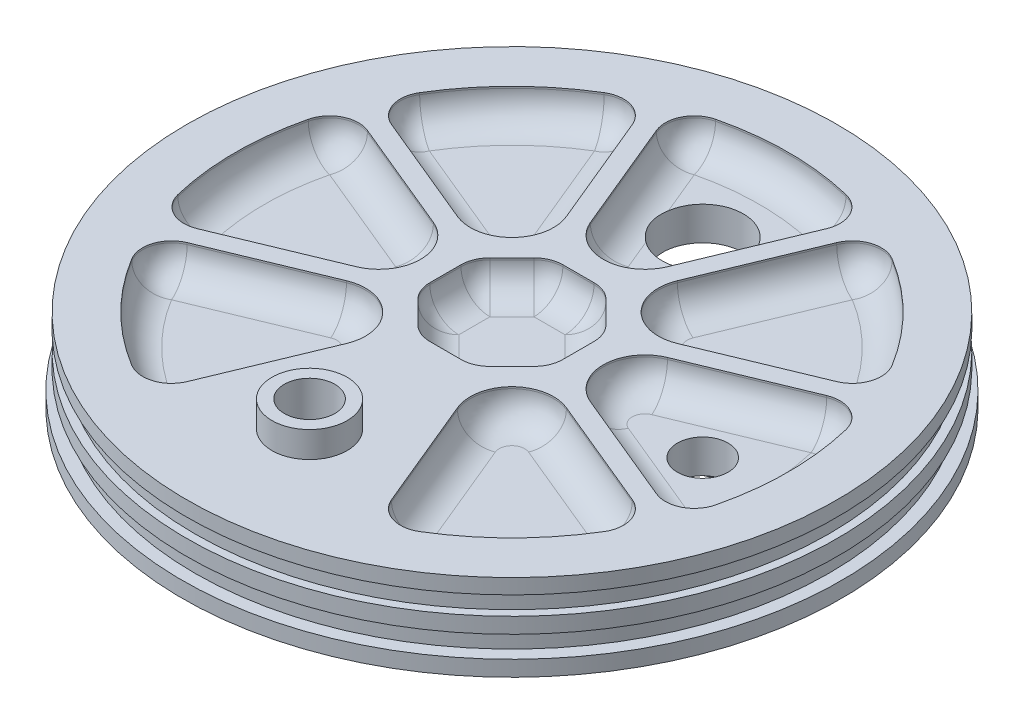
SolidWorks part; units mm, degrees
material "6061-T6 (SS)"
ref_plane "Front Plane" through (0, 0, 0) normal (0, 0, 1) x (1, 0, 0)
ref_plane "Top Plane" through (0, 0, 0) normal (0, 1, 0) x (1, 0, 0)
ref_plane "Right Plane" through (0, 0, 0) normal (1, 0, 0) x (0, 0, -1)
sketch "Sketch1" plane through (0, 0, 0) normal (0, 0, 1) x (1, 0, 0)
  line L0 (0, 48.1922) -> (0, -25.6743) construction
  line L1 (0, 0) -> (72.39, 0)
  line L2 (72.39, 0) -> (72.39, 3.429)
  line L3 (72.39, 3.429) -> (69.6468, 3.429)
  line L4 (69.6468, 3.429) -> (69.6468, 7.493)
  line L5 (69.6468, 7.493) -> (71.4248, 7.493)
  line L6 (71.4248, 7.493) -> (71.4248, 10.922)
  line L7 (71.4248, 10.922) -> (69.6468, 10.922)
  line L8 (60.7568, 18.288) -> (60.7568, 11.557)
  line L9 (60.7568, 11.557) -> (0, 11.557)
  line L10 (0, 11.557) -> (0, 0)
  line L11 (69.6468, 10.922) -> (69.6468, 14.986)
  line L12 (69.6468, 14.986) -> (71.4248, 14.986)
  line L13 (71.4248, 14.986) -> (71.4248, 18.288)
  line L14 (71.4248, 18.288) -> (60.7568, 18.288)
  dimension "D2" = 4.064
  dimension "D5" = 11.557
  dimension "D7" = 4.064
  dimension "D4" = 3.429
  dimension "D8" = 3.302
  dimension "D6" = 8.89
  dimension "D1" = 72.39
  dimension "D9" = 1.778
  dimension "D3" = 69.6468
revolve "Revolve1" add sketch "Sketch1" angle 360 about L0
sketch "Sketch6" plane through (0, 0, 0) normal (0, -1, 0) x (1, 0, 0)
  circle A0 centre (0, 0) radius 66.04
  dimension "D1" = 132.08
extrude "Boss-Extrude1" add sketch "Sketch6" along normal blind 2.54
hole_wizard "Pipe Tap Drill for 1/4 Tap - GN2" positions "Sketch2" profile "Sketch3" hole size "1/4" standard "ANSI Inch" end condition through all
sketch "Sketch2" plane through (0, 11.557, 0) normal (0, 1, 0) x (1, 0, 0)
  point P4 (0, -44.45)
  dimension "D1" = 44.45
sketch "Sketch3" plane through (0, 11.557, 44.45) normal (1, 0, 0) x (0, 0, 1)
  line L0 (0, 0) -> (0, 14.097)
  line L1 (0, 14.097) -> (5.5626, 14.097)
  line L2 (5.5626, 14.097) -> (5.5626, 0)
  line L5 (5.5626, 0) -> (0, 0)
  line L11 (0, -6.35) -> (0, 107.95) construction
  dimension "Thru Hole Dia." = 11.1252
  dimension "Thru Hole Depth" = 14.097
fillet "CNC ID Fillet" [suppressed] radius 0.4064
fillet "CNC OD Fillet" [suppressed] radius 0.127
chamfer "CNC Chamfers" [suppressed] distance 0.508 angle 65
sketch "Sketch15" plane through (0, -2.54, 0) normal (0, -1, 0) x (1, 0, 0)
  circle A0 centre (0, 44.45) radius 8.255
  circle A1 centre (0, 44.45) radius 5.5626 construction
  circle A2 centre (0, 44.45) radius 5.5626
  dimension "D1" = 16.51
extrude "Boss-Extrude2" add sketch "Sketch15" against normal blind 12.446 from surface starting at face at (0, 11.557, 50.0126)
sketch "Sketch18" plane through (0, 18.288, 0) normal (0, 1, 0) x (1, 0, 0)
  line L0 (0, 0) -> (0, 60.7568) construction
  line L1 (0, 0) -> (23.2506, 56.132) construction
  line L2 (0, 0) -> (56.132, 23.2506) construction
  line L3 (0, 0) -> (56.132, -23.2506) construction
  line L4 (0, 0) -> (23.2506, -56.132) construction
  line L5 (0, 0) -> (-23.2506, -56.132) construction
  line L6 (0, 0) -> (-56.132, -23.2506) construction
  line L7 (0, 0) -> (-56.132, 23.2506) construction
  line L8 (0, 0) -> (-23.2506, 56.132) construction
  line L9 (-8.448, 25.705) -> (-21.3733, 56.9096)
  line L10 (12.2026, 24.1498) -> (25.1279, 55.3544)
  line L11 (25.705, 8.448) -> (56.9096, 21.3733)
  line L12 (24.1498, -12.2026) -> (55.3544, -25.1279)
  line L13 (8.448, -25.705) -> (21.3733, -56.9096)
  line L14 (-12.2026, -24.1498) -> (-25.1279, -55.3544)
  line L15 (-25.705, -8.448) -> (-56.9096, -21.3733)
  line L16 (-24.1498, 12.2026) -> (-55.3544, 25.1279)
  line L17 (-12.2026, 24.1498) -> (-25.1279, 55.3544)
  line L18 (8.448, 25.705) -> (21.3733, 56.9096)
  line L19 (24.1498, 12.2026) -> (55.3544, 25.1279)
  line L20 (25.705, -8.448) -> (56.9096, -21.3733)
  line L21 (12.2026, -24.1498) -> (25.1279, -55.3544)
  line L22 (-8.448, -25.705) -> (-21.3733, -56.9096)
  line L23 (-24.1498, -12.2026) -> (-55.3544, -25.1279)
  line L24 (-25.705, 8.448) -> (-56.9096, 21.3733)
  line L25 (1.8773, 0.7776) -> (-21.3733, 56.9096) construction
  line L26 (-1.8773, 0.7776) -> (21.3733, 56.9096) construction
  line L27 (1.8773, -0.7776) -> (25.1279, 55.3544) construction
  line L28 (-0.7776, 1.8773) -> (55.3544, 25.1279) construction
  line L29 (0.7776, -1.8773) -> (56.9096, 21.3733) construction
  line L30 (0.7776, 1.8773) -> (56.9096, -21.3733) construction
  line L31 (-0.7776, -1.8773) -> (55.3544, -25.1279) construction
  line L32 (1.8773, 0.7776) -> (25.1279, -55.3544) construction
  line L33 (-1.8773, -0.7776) -> (21.3733, -56.9096) construction
  line L34 (1.8773, -0.7776) -> (-21.3733, -56.9096) construction
  line L35 (-1.8773, 0.7776) -> (-25.1279, -55.3544) construction
  line L36 (0.7776, -1.8773) -> (-55.3544, -25.1279) construction
  line L37 (-0.7776, 1.8773) -> (-56.9096, -21.3733) construction
  line L38 (-0.7776, -1.8773) -> (-56.9096, 21.3733) construction
  line L39 (0.7776, 1.8773) -> (-55.3544, 25.1279) construction
  line L40 (-1.8773, -0.7776) -> (-25.1279, 55.3544) construction
  line L42 (6.0496, 14.605) -> (-6.0496, 14.605)
  line L43 (-6.0496, 14.605) -> (-14.605, 6.0496)
  line L44 (-14.605, 6.0496) -> (-14.605, -6.0496)
  line L45 (-14.605, -6.0496) -> (-6.0496, -14.605)
  line L46 (-6.0496, -14.605) -> (6.0496, -14.605)
  line L47 (6.0496, -14.605) -> (14.605, -6.0496)
  line L48 (14.605, -6.0496) -> (14.605, 6.0496)
  line L49 (14.605, 6.0496) -> (6.0496, 14.605)
  circle A0 centre (0, 0) radius 60.7568 construction
  circle A1 centre (0, 0) radius 60.7568
  arc A2 (-8.448, 25.705) -> (8.448, 25.705) centre (0, 29.2043) ccw
  arc A3 (12.2026, 24.1498) -> (24.1498, 12.2026) centre (20.6506, 20.6506) ccw
  arc A4 (25.705, 8.448) -> (25.705, -8.448) centre (29.2043, 0) ccw
  arc A5 (24.1498, -12.2026) -> (12.2026, -24.1498) centre (20.6506, -20.6506) ccw
  arc A6 (8.448, -25.705) -> (-8.448, -25.705) centre (0, -29.2043) ccw
  arc A7 (-12.2026, -24.1498) -> (-24.1498, -12.2026) centre (-20.6506, -20.6506) ccw
  arc A8 (-25.705, -8.448) -> (-25.705, 8.448) centre (-29.2043, 0) ccw
  arc A9 (-24.1498, 12.2026) -> (-12.2026, 24.1498) centre (-20.6506, 20.6506) ccw
  circle A10 centre (0, 0) radius 14.605 construction
  circle A11 centre (0, -44.45) radius 5.5626 construction
  circle A12 centre (0, -44.45) radius 5.5626
  point P7 (0, 0)
  point P15 (0, 0)
  dimension "D5" = 9.144
  dimension "D6" = 29.21
  dimension "D1" = 22.5
  dimension "D3" = 2.032
  dimension "D4" = 2.032
  dimension "D2" = 8
extrude "Boss-Extrude10" add sketch "Sketch18" against normal up to surface (6.731 mm away) contours A9 L16 L24 A8 L15 L23 A7 L14 L22 A6 L13 L21 A5 L12 L20 A4 L11 L19 A3 L10 L18 A2 L9 L17 | L13 A6 L22 region at (0, 18.288, -18.4515) region at (-14.359, 18.288, 41.5174) up to face at (8.255, 11.557, 44.45)
fillet "Fillet14" radius 6.35 58 edges at (-14.9041, 11.557, -41.2916) (0, 11.557, -20.0603) (14.1848, 11.557, -14.1848) (18.6588, 11.557, -39.7364) (42.9615, 11.557, -42.9615) (39.7364, 11.557, -18.6588) (20.0603, 11.557, 0) (41.2916, 11.557, -14.9041) (60.7568, 11.557, 0) (41.2916, 11.557, 14.9041) (-18.6588, 11.557, -39.7364) (-14.1848, 11.557, -14.1848) (-39.7364, 11.557, -18.6588) (-42.9615, 11.557, -42.9615) (-20.0603, 11.557, 0) (-41.2916, 11.557, 14.9041) (-60.7568, 11.557, 0) (-41.2916, 11.557, -14.9041) (-14.1848, 11.557, 14.1848) (-18.6588, 11.557, 39.7364) (-42.9615, 11.557, 42.9615) (-39.7364, 11.557, 18.6588) (14.1848, 11.557, 14.1848) (39.7364, 11.557, 18.6588) (42.9615, 11.557, 42.9615) (18.6588, 11.557, 39.7364) (14.9041, 11.557, -41.2916) (0, 11.557, -60.7568) (14.605, 11.557, 0) (10.3273, 11.557, 10.3273) (0, 11.557, 14.605) (-10.3273, 11.557, 10.3273) (-14.605, 11.557, 0) (-10.3273, 11.557, -10.3273) (0, 11.557, -14.605) (10.3273, 11.557, -10.3273) (6.0496, 14.9225, 14.605) (-6.0496, 14.9225, 14.605) (-14.605, 14.9225, 6.0496) (-14.605, 14.9225, -6.0496) (-6.0496, 14.9225, -14.605) (6.0496, 14.9225, -14.605) (14.605, 14.9225, -6.0496) (14.605, 14.9225, 6.0496) (-25.1149, 14.9225, -55.3229) (-55.3229, 14.9225, -25.1149) (-56.8782, 14.9225, 21.3603) (-56.8782, 14.9225, -21.3603) (-55.3229, 14.9225, 25.1149) (-25.1149, 14.9225, 55.3229) (25.1149, 14.9225, 55.3229) (55.3229, 14.9225, 25.1149) (56.8782, 14.9225, 21.3603) (56.8782, 14.9225, -21.3603) (55.3229, 14.9225, -25.1149) (25.1149, 14.9225, -55.3229) (21.3603, 14.9225, -56.8782) (-21.3603, 14.9225, -56.8782)
sketch "Sketch19" plane through (0, 18.288, 0) normal (0, 1, 0) x (1, 0, 0)
  circle A0 centre (0, 0) radius 65.111 construction
  text T0 "IF YOURE READING THIS YOUVE MADE A SEVERE ERROR                                                                                     RELEVANT EXPERIENCE"
sketch "Sketch20" plane through (0, -2.54, 0) normal (0, -1, 0) x (1, 0, 0)
  line L3 (-8.448, 25.705) -> (-21.3733, 56.9096) construction
  line L7 (8.448, 25.705) -> (21.3733, 56.9096) construction
  line L11 (-8.448, 25.705) -> (-21.3733, 56.9096)
  line L13 (8.448, 25.705) -> (21.3733, 56.9096)
  line L16 (-50.4428, -18.6947) -> (-25.705, -8.448)
  line L17 (-25.705, 8.448) -> (-50.4428, 18.6947)
  line L18 (-50.4428, -18.6947) -> (-25.705, -8.448)
  line L19 (-25.705, 8.448) -> (-50.4428, 18.6947)
  line L31 (-12.2026, 24.1498) -> (-22.4493, 48.8876)
  line L35 (-48.8876, 22.4493) -> (-24.1498, 12.2026)
  line L39 (-12.2026, 24.1498) -> (-22.4493, 48.8876)
  line L43 (-48.8876, 22.4493) -> (-24.1498, 12.2026)
  line L47 (24.1498, 12.2026) -> (48.8876, 22.4493)
  line L52 (22.4493, 48.8876) -> (12.2026, 24.1498)
  line L53 (7.9095, -12.7451) -> (12.7451, -7.9095)
  line L54 (14.605, -3.4193) -> (14.605, 3.4193)
  line L55 (12.7451, 7.9095) -> (7.9095, 12.7451)
  line L56 (3.4193, 14.605) -> (-3.4193, 14.605)
  line L57 (-7.9095, 12.7451) -> (-12.7451, 7.9095)
  line L58 (-14.605, 3.4193) -> (-14.605, -3.4193)
  line L59 (-12.7451, -7.9095) -> (-7.9095, -12.7451)
  line L60 (-3.4193, -14.605) -> (3.4193, -14.605)
  line L61 (7.9095, -12.7451) -> (12.7451, -7.9095)
  line L62 (14.605, -3.4193) -> (14.605, 3.4193)
  line L63 (12.7451, 7.9095) -> (7.9095, 12.7451)
  line L64 (3.4193, 14.605) -> (-3.4193, 14.605)
  line L65 (-7.9095, 12.7451) -> (-12.7451, 7.9095)
  line L66 (-14.605, 3.4193) -> (-14.605, -3.4193)
  line L67 (-12.7451, -7.9095) -> (-7.9095, -12.7451)
  line L68 (-3.4193, -14.605) -> (3.4193, -14.605)
  line L69 (24.1498, 12.2026) -> (48.8876, 22.4493)
  line L70 (22.4493, 48.8876) -> (12.2026, 24.1498)
  line L71 (25.705, -8.448) -> (50.4428, -18.6947)
  line L72 (50.4428, 18.6947) -> (25.705, 8.448)
  line L73 (25.705, -8.448) -> (50.4428, -18.6947)
  line L74 (50.4428, 18.6947) -> (25.705, 8.448)
  line L75 (12.2026, -24.1498) -> (22.4493, -48.8876)
  line L76 (48.8876, -22.4493) -> (24.1498, -12.2026)
  line L77 (12.2026, -24.1498) -> (22.4493, -48.8876)
  line L78 (48.8876, -22.4493) -> (24.1498, -12.2026)
  line L79 (-8.448, -25.705) -> (-18.6947, -50.4428)
  line L80 (18.6947, -50.4428) -> (8.448, -25.705)
  line L81 (-8.448, -25.705) -> (-18.6947, -50.4428)
  line L82 (18.6947, -50.4428) -> (8.448, -25.705)
  line L83 (-24.1498, -12.2026) -> (-48.8876, -22.4493)
  line L84 (-22.4493, -48.8876) -> (-12.2026, -24.1498)
  line L85 (-24.1498, -12.2026) -> (-48.8876, -22.4493)
  line L86 (-22.4493, -48.8876) -> (-12.2026, -24.1498)
  circle A1 centre (0, 0) radius 60.7568 construction
  arc A3 (-8.448, 25.705) -> (8.448, 25.705) centre (0, 29.2043) ccw construction
  circle A8 centre (0, 0) radius 60.7568
  arc A40 (-8.448, 25.705) -> (8.448, 25.705) centre (0, 29.2043) ccw
  arc A127 (-59.0438, 14.3253) -> (-59.0438, -14.3253) centre (0, 0) ccw
  arc A128 (-59.0438, -14.3253) -> (-50.4428, -18.6947) centre (-52.8729, -12.8281) ccw
  arc A129 (-25.705, -8.448) -> (-25.705, 8.448) centre (-29.2043, 0) ccw
  arc A130 (-50.4428, 18.6947) -> (-59.0438, 14.3253) centre (-52.8729, 12.8281) ccw
  arc A131 (-59.0438, 14.3253) -> (-59.0438, -14.3253) centre (0, 0) ccw
  arc A132 (-59.0438, -14.3253) -> (-50.4428, -18.6947) centre (-52.8729, -12.8281) ccw
  arc A133 (-25.705, -8.448) -> (-25.705, 8.448) centre (-29.2043, 0) ccw
  arc A134 (-50.4428, 18.6947) -> (-59.0438, 14.3253) centre (-52.8729, 12.8281) ccw
  arc A135 (-22.4493, 48.8876) -> (-31.6208, 51.8798) centre (-28.316, 46.4576) ccw
  arc A136 (-31.6208, 51.8798) -> (-51.8798, 31.6208) centre (0, 0) ccw
  arc A137 (-51.8798, 31.6208) -> (-48.8876, 22.4493) centre (-46.4576, 28.316) ccw
  arc A138 (-24.1498, 12.2026) -> (-12.2026, 24.1498) centre (-20.6506, 20.6506) ccw
  arc A139 (12.7451, -7.9095) -> (14.605, -3.4193) centre (8.255, -3.4193) ccw
  arc A140 (14.605, 3.4193) -> (12.7451, 7.9095) centre (8.255, 3.4193) ccw
  arc A141 (7.9095, 12.7451) -> (3.4193, 14.605) centre (3.4193, 8.255) ccw
  arc A142 (-3.4193, 14.605) -> (-7.9095, 12.7451) centre (-3.4193, 8.255) ccw
  arc A143 (-12.7451, 7.9095) -> (-14.605, 3.4193) centre (-8.255, 3.4193) ccw
  arc A144 (-14.605, -3.4193) -> (-12.7451, -7.9095) centre (-8.255, -3.4193) ccw
  arc A145 (-7.9095, -12.7451) -> (-3.4193, -14.605) centre (-3.4193, -8.255) ccw
  arc A146 (3.4193, -14.605) -> (7.9095, -12.7451) centre (3.4193, -8.255) ccw
  arc A147 (12.7451, -7.9095) -> (14.605, -3.4193) centre (8.255, -3.4193) ccw
  arc A148 (14.605, 3.4193) -> (12.7451, 7.9095) centre (8.255, 3.4193) ccw
  arc A149 (7.9095, 12.7451) -> (3.4193, 14.605) centre (3.4193, 8.255) ccw
  arc A150 (-3.4193, 14.605) -> (-7.9095, 12.7451) centre (-3.4193, 8.255) ccw
  arc A151 (-12.7451, 7.9095) -> (-14.605, 3.4193) centre (-8.255, 3.4193) ccw
  arc A152 (-14.605, -3.4193) -> (-12.7451, -7.9095) centre (-8.255, -3.4193) ccw
  arc A153 (-7.9095, -12.7451) -> (-3.4193, -14.605) centre (-3.4193, -8.255) ccw
  arc A154 (3.4193, -14.605) -> (7.9095, -12.7451) centre (3.4193, -8.255) ccw
  arc A155 (-22.4493, 48.8876) -> (-31.6208, 51.8798) centre (-28.316, 46.4576) ccw
  arc A156 (-31.6208, 51.8798) -> (-51.8798, 31.6208) centre (0, 0) ccw
  arc A157 (-51.8798, 31.6208) -> (-48.8876, 22.4493) centre (-46.4576, 28.316) ccw
  arc A158 (-24.1498, 12.2026) -> (-12.2026, 24.1498) centre (-20.6506, 20.6506) ccw
  arc A159 (48.8876, 22.4493) -> (51.8798, 31.6208) centre (46.4576, 28.316) ccw
  arc A160 (51.8798, 31.6208) -> (31.6208, 51.8798) centre (0, 0) ccw
  arc A161 (31.6208, 51.8798) -> (22.4493, 48.8876) centre (28.316, 46.4576) ccw
  arc A162 (12.2026, 24.1498) -> (24.1498, 12.2026) centre (20.6506, 20.6506) ccw
  arc A163 (48.8876, 22.4493) -> (51.8798, 31.6208) centre (46.4576, 28.316) ccw
  arc A164 (51.8798, 31.6208) -> (31.6208, 51.8798) centre (0, 0) ccw
  arc A165 (31.6208, 51.8798) -> (22.4493, 48.8876) centre (28.316, 46.4576) ccw
  arc A166 (12.2026, 24.1498) -> (24.1498, 12.2026) centre (20.6506, 20.6506) ccw
  arc A167 (50.4428, -18.6947) -> (59.0438, -14.3253) centre (52.8729, -12.8281) ccw
  arc A168 (59.0438, -14.3253) -> (59.0438, 14.3253) centre (0, 0) ccw
  arc A169 (59.0438, 14.3253) -> (50.4428, 18.6947) centre (52.8729, 12.8281) ccw
  arc A170 (25.705, 8.448) -> (25.705, -8.448) centre (29.2043, 0) ccw
  arc A171 (50.4428, -18.6947) -> (59.0438, -14.3253) centre (52.8729, -12.8281) ccw
  arc A172 (59.0438, -14.3253) -> (59.0438, 14.3253) centre (0, 0) ccw
  arc A173 (59.0438, 14.3253) -> (50.4428, 18.6947) centre (52.8729, 12.8281) ccw
  arc A174 (25.705, 8.448) -> (25.705, -8.448) centre (29.2043, 0) ccw
  arc A175 (22.4493, -48.8876) -> (31.6208, -51.8798) centre (28.316, -46.4576) ccw
  arc A176 (31.6208, -51.8798) -> (51.8798, -31.6208) centre (0, 0) ccw
  arc A177 (51.8798, -31.6208) -> (48.8876, -22.4493) centre (46.4576, -28.316) ccw
  arc A178 (24.1498, -12.2026) -> (12.2026, -24.1498) centre (20.6506, -20.6506) ccw
  arc A179 (22.4493, -48.8876) -> (31.6208, -51.8798) centre (28.316, -46.4576) ccw
  arc A180 (31.6208, -51.8798) -> (51.8798, -31.6208) centre (0, 0) ccw
  arc A181 (51.8798, -31.6208) -> (48.8876, -22.4493) centre (46.4576, -28.316) ccw
  arc A182 (24.1498, -12.2026) -> (12.2026, -24.1498) centre (20.6506, -20.6506) ccw
  arc A183 (-18.6947, -50.4428) -> (-14.3253, -59.0438) centre (-12.8281, -52.8729) ccw
  arc A184 (-14.3253, -59.0438) -> (14.3253, -59.0438) centre (0, 0) ccw
  arc A185 (14.3253, -59.0438) -> (18.6947, -50.4428) centre (12.8281, -52.8729) ccw
  arc A186 (8.448, -25.705) -> (-8.448, -25.705) centre (0, -29.2043) ccw
  arc A187 (-18.6947, -50.4428) -> (-14.3253, -59.0438) centre (-12.8281, -52.8729) ccw
  arc A188 (-14.3253, -59.0438) -> (14.3253, -59.0438) centre (0, 0) ccw
  arc A189 (14.3253, -59.0438) -> (18.6947, -50.4428) centre (12.8281, -52.8729) ccw
  arc A190 (8.448, -25.705) -> (-8.448, -25.705) centre (0, -29.2043) ccw
  arc A191 (-48.8876, -22.4493) -> (-51.8798, -31.6208) centre (-46.4576, -28.316) ccw
  arc A192 (-51.8798, -31.6208) -> (-31.6208, -51.8798) centre (0, 0) ccw
  arc A193 (-31.6208, -51.8798) -> (-22.4493, -48.8876) centre (-28.316, -46.4576) ccw
  arc A194 (-12.2026, -24.1498) -> (-24.1498, -12.2026) centre (-20.6506, -20.6506) ccw
  arc A195 (-48.8876, -22.4493) -> (-51.8798, -31.6208) centre (-46.4576, -28.316) ccw
  arc A196 (-51.8798, -31.6208) -> (-31.6208, -51.8798) centre (0, 0) ccw
  arc A197 (-31.6208, -51.8798) -> (-22.4493, -48.8876) centre (-28.316, -46.4576) ccw
  arc A198 (-12.2026, -24.1498) -> (-24.1498, -12.2026) centre (-20.6506, -20.6506) ccw
  dimension "D1" = 0
  dimension "D2" = 0
  dimension "D3" = 0
  dimension "D4" = 0
  dimension "D5" = 0
  dimension "D6" = 0
  dimension "D7" = 0
  dimension "D8" = 0
extrude "Cut-Extrude1" cut sketch "Sketch20" against normal blind 6.731
fillet "Fillet16" radius 6.35 64 edges at (14.9041, 4.191, 41.2916) (0, 4.191, 20.0603) (26.3465, 4.191, 52.4944) (42.9615, 4.191, 42.9615) (52.4944, 4.191, 26.3465) (36.5187, 4.191, 17.326) (14.1848, 4.191, 14.1848) (17.326, 4.191, 36.5187) (55.7489, 4.191, 18.4894) (60.7568, 4.191, 0) (55.7489, 4.191, -18.4894) (38.0739, 4.191, -13.5713) (20.0603, 4.191, 0) (38.0739, 4.191, 13.5713) (52.4944, 4.191, -26.3465) (42.9615, 4.191, -42.9615) (26.3465, 4.191, -52.4944) (17.326, 4.191, -36.5187) (14.1848, 4.191, -14.1848) (36.5187, 4.191, -17.326) (18.4894, 4.191, -55.7489) (0, 4.191, -60.7568) (-18.4894, 4.191, -55.7489) (-13.5713, 4.191, -38.0739) (0, 4.191, -20.0603) (13.5713, 4.191, -38.0739) (-26.3465, 4.191, -52.4944) (-42.9615, 4.191, -42.9615) (-52.4944, 4.191, -26.3465) (-36.5187, 4.191, -17.326) (-14.1848, 4.191, -14.1848) (-17.326, 4.191, -36.5187) (-20.0603, 4.191, 0) (-38.0739, 4.191, -13.5713) (-55.7489, 4.191, -18.4894) (-60.7568, 4.191, 0) (-55.7489, 4.191, 18.4894) (-38.0739, 4.191, 13.5713) (-52.4944, 4.191, 26.3465) (-42.9615, 4.191, 42.9615) (-26.3465, 4.191, 52.4944) (-17.326, 4.191, 36.5187) (-14.1848, 4.191, 14.1848) (-36.5187, 4.191, 17.326) (-5.8494, 4.191, -14.1216) (-10.3273, 4.191, -10.3273) (-14.1216, 4.191, -5.8494) (-14.605, 4.191, 0) (-14.1216, 4.191, 5.8494) (-10.3273, 4.191, 10.3273) (-5.8494, 4.191, 14.1216) (0, 4.191, 14.605) (5.8494, 4.191, 14.1216) (10.3273, 4.191, 10.3273) (14.1216, 4.191, 5.8494) (14.605, 4.191, 0) (14.1216, 4.191, -5.8494) (10.3273, 4.191, -10.3273) (5.8494, 4.191, -14.1216) (0, 4.191, -14.605) (21.3603, 0.8255, 56.8782) (-21.3603, 0.8255, 56.8782) (-14.9041, 4.191, 41.2916) (0, 4.191, 60.7568)
hole_wizard "Pipe Tap Drill for 1/2 Tap - 750psi vent stem" positions "Sketch13" profile "Sketch14" hole size "1/2" standard "ANSI Inch" end condition through all
sketch "Sketch13" plane through (0, -2.54, 0) normal (0, -1, 0) x (-1, 0, 0)
  point P4 (0, 41.91)
  dimension "D1" = 41.91
sketch "Sketch14" plane through (0, -2.54, -41.91) normal (1, 0, 0) x (0, 0, -1)
  line L0 (0, 0) -> (0, 26.543)
  line L1 (0, 26.543) -> (8.9281, 26.543)
  line L2 (8.9281, 26.543) -> (8.9281, 0)
  line L5 (8.9281, 0) -> (0, 0)
  line L11 (0, -6.35) -> (0, 107.95) construction
  dimension "Thru Hole Dia." = 17.8562
  dimension "Thru Hole Depth" = 26.543
sketch "Sketch16" plane through (0, 4.191, 0) normal (0, -1, 0) x (1, 0, 0)
  line L0 (0, 44.45) -> (0, -41.91) construction
  line L1 (-6.35, 44.45) -> (6.35, 44.45) construction
  line L2 (-9.4223, 1.27) -> (9.4223, 1.27) construction
  line L3 (25.4, -35.56) -> (-25.4, -35.56) construction
  arc A0 (-6.35, 44.45) -> (6.35, 44.45) centre (0, 44.45) ccw
  arc A1 (-6.35, -41.91) -> (6.35, -41.91) centre (0, -41.91) cw
  arc A2 (6.35, -41.91) -> (-6.347, -42.1056) centre (0, -41.91) cw
  arc A3 (-6.35, 44.45) -> (6.35, 44.45) centre (0, 44.45) cw
  text T0 "GN2" font "Century Gothic" height in points 12
  text T1 "VENT\r\n" font "Century Gothic" height in points 16
  point P7 (0, 38.1)
  point P14 (0, 1.27)
  dimension "D1" = 6.35
sketch "Sketch21" plane through (0, -2.54, 0) normal (0, -1, 0) x (-1, 0, 0)
  circle A0 centre (0, 0) radius 61.5526 construction
  text T0 "DEFLAGRATION RESEARCH LABORATORY                                        THIS SIDE UP                                                   RELEVANT EXPERIENCE"
fillet "Fillet17" [suppressed] radius 3.175
hole_wizard "Pipe Tap Drill for 1/4 Tap - 150psi vent stem" positions "Sketch22" profile "Sketch23" hole size "1/4" standard "ANSI Inch" end condition through all
sketch "Sketch22" plane through (0, 4.191, 0) normal (0, -1, 0) x (-1, 0, 0)
  point P4 (-41.91, 0)
  dimension "D1" = 41.91
sketch "Sketch23" plane through (41.91, 4.191, 0) normal (1, 0, 0) x (0, 0, -1)
  line L0 (0, 0) -> (0, 19.812)
  line L1 (0, 19.812) -> (5.5626, 19.812)
  line L2 (5.5626, 19.812) -> (5.5626, 0)
  line L5 (5.5626, 0) -> (0, 0)
  line L11 (0, -6.35) -> (0, 107.95) construction
  dimension "Thru Hole Dia." = 11.1252
  dimension "Thru Hole Depth" = 19.812
equation "\"D3@Sketch1\"=5.484/2"
equation "\"D1@Sketch1\"=5.7/2"
